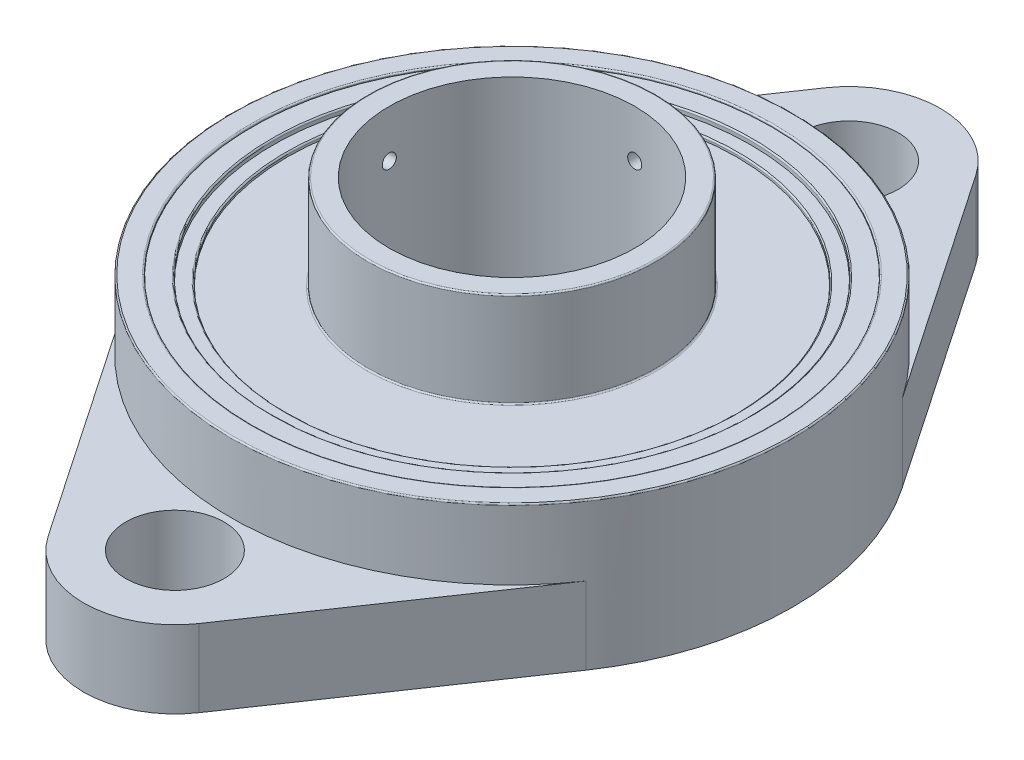
SolidWorks part; units mm, degrees
ref_plane "Front Plane" through (0, 0, 0) normal (0, 0, 1) x (1, 0, 0)
ref_plane "Top Plane" through (0, 0, 0) normal (0, 1, 0) x (1, 0, 0)
ref_plane "Right Plane" through (0, 0, 0) normal (1, 0, 0) x (0, 0, -1)
sketch "Sketch1" plane through (0, 0, 0) normal (0, 1, 0) x (1, 0, 0)
  line L0 (0, -61) -> (0, 61) construction
  line L1 (0, 0) -> (-50000, 0) construction
  line L2 (33.0719, -22.5) -> (10.7484, -55.3125)
  line L3 (33.0719, 22.5) -> (10.7484, 55.3125)
  line L4 (-33.0719, -22.5) -> (-10.7484, -55.3125)
  line L5 (-33.0719, 22.5) -> (-10.7484, 55.3125)
  circle A0 centre (0, 0) radius 40
  circle A1 centre (0, 0) radius 17.5
  circle A2 centre (0, 48) radius 7
  circle A3 centre (0, 0) radius 37
  circle A4 centre (0, 0) radius 20.5
  arc A5 (10.7484, 55.3125) -> (-10.7484, 55.3125) centre (0, 48) ccw
  circle A6 centre (0, -48) radius 7
  arc A7 (-10.7484, -55.3125) -> (10.7484, -55.3125) centre (0, -48) ccw
  circle A8 centre (0, 0) radius 34
  circle A9 centre (0, 0) radius 32
  point P6 (0, 0)
  dimension "D1" = 35
  dimension "D2" = 80
  dimension "D5" = 14
  dimension "D3" = 122
  dimension "D4" = 96
  dimension "D6" = 3
  dimension "D7" = 3
  dimension "D8" = 3
  dimension "D9" = 2
extrude "A1" add sketch "Sketch1" along normal blind 11 contours L4 A7 L2 A0 A6 | A0 A3 | L3 A5 L5 A0 A2 region at (21.2774, 0, 38.4758) region at (0, 0, 38.8686) region at (-21.2774, 0, -38.4758)
extrude "A" add sketch "Sketch1<3>" along normal blind 21 contours A0 A3 region at (0, 0, 38.8686)
sketch "Sketch1<3>" plane through (0, 0, 0) normal (0, 1, 0) x (1, 0, 0) same geometry as "Sketch1"
extrude "A0" add sketch "Sketch1<4>" along normal blind 33 contours A4 A1 region at (-19.9202, 0, 0)
sketch "Sketch1<4>" plane through (0, 0, 0) normal (0, 1, 0) x (1, 0, 0) same geometry as "Sketch1"
extrude "Bearing outer d" add sketch "Sketch1<7>" along normal blind 18 from offset 2 separate body contours A8 A9 region at (-33.0383, 0, 0)
sketch "Sketch1<7>" plane through (0, 0, 0) normal (0, 1, 0) x (1, 0, 0) same geometry as "Sketch1"
extrude "Boss-Extrude6" add sketch "Sketch1<8>" along normal blind 19.5 from offset 1.2 contours A3 A8 region at (-35.9535, 0, 0)
sketch "Sketch1<8>" plane through (0, 0, 0) normal (0, 1, 0) x (1, 0, 0) same geometry as "Sketch1"
extrude "Boss-Extrude7" add sketch "Sketch1<9>" along normal blind 18 from offset 1.5 contours A9 A4 region at (-31.0949, 0, 0)
sketch "Sketch1<9>" plane through (0, 0, 0) normal (0, 1, 0) x (1, 0, 0) same geometry as "Sketch1"
sketch "Sketch2" plane through (0, 0, 0) normal (1, 0, 0) x (0, 0, -1)
  line L0 (0, 0) -> (0, 50000) construction
  line L1 (-22.5, 0) -> (22.5, 0) construction
  line L2 (20.5, 26.25) -> (-20.5, 26.25) construction
  line L3 (20.5, 19.5) -> (20.5, 33) construction
  line L4 (-20.5, 33) -> (-20.5, 19.5) construction
  circle A0 centre (0, 26.25) radius 1
  point P4 (0, 0)
  dimension "D1" = 2
extrude "Cut-Extrude1" cut sketch "Sketch2" against normal up to next
sketch "Sketch3" plane through (0, 0, 0) normal (0, 0, 1) x (1, 0, 0)
  line L0 (0, 0) -> (0, 50000) construction
  line L1 (6, 26.25) -> (-49994, 26.25) construction
  line L3 (20.5, 19.5) -> (20.5, 33) construction
  circle A0 centre (0, 26.25) radius 1
  point P7 (20.5, 26.25)
  dimension "D1" = 2
extrude "Cut-Extrude2" cut sketch "Sketch3" against normal up to next
fillet "Fillet1" radius 0.2 1 edges at (0, 20, 32)
fillet "Fillet2" radius 0.2 5 edges at (0, 33, 20.5) (0, 19.5, 20.5) (0, 21, 40) (0, 21, 37) (0, 20.7, 34)
equation "\"A\"= \"D1@A\""
equation "\"A0\"= \"D1@A0\""
equation "\"A1\"= \"D1@A1\""
equation "\"D1@Bearing outer d\"=\"D1@Boss-Extrude6\" - 1.5"
equation "\"D1@Boss-Extrude6\"=\"D1@A\" - 1.5"
equation "\"D1@Boss-Extrude7\"= \"D1@Bearing outer d\""
equation "\"S\"= \"D19@Boss-Extrude7\""
equation "\"D19@Boss-Extrude6\"=\"D19@Boss-Extrude7\" - 0.3"
equation "\"H\"= \"D3@Sketch1\""
equation "\"J\"= \"D4@Sketch1\""
equation "\"L\"= \"D2@Sketch1\""
equation "\"N\"= \"D5@Sketch1\""
equation "\"d\"= \"D1@Sketch1\""
